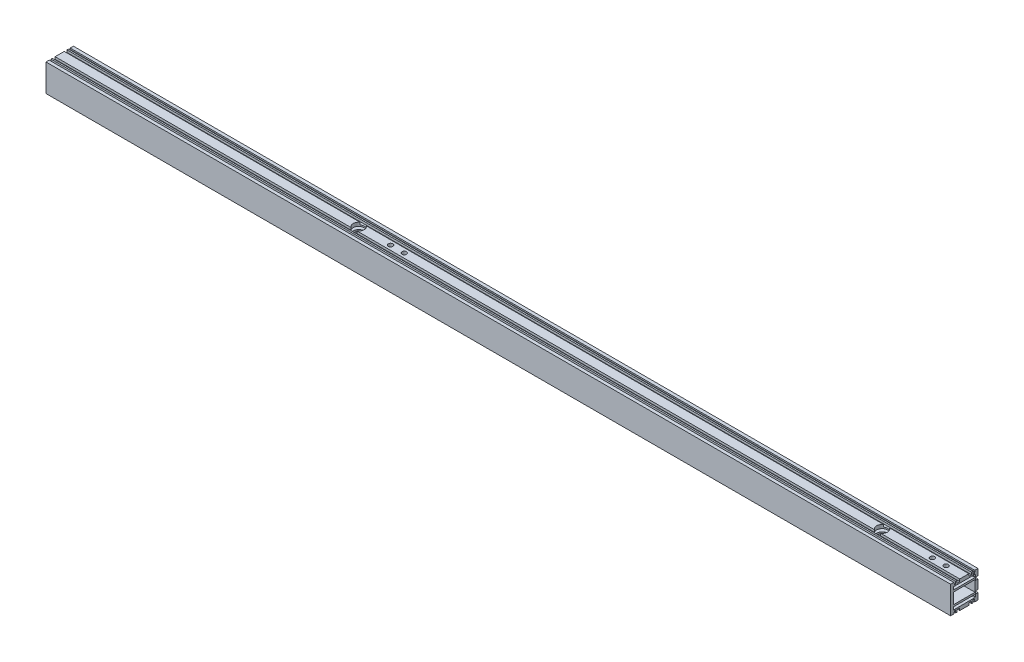
SolidWorks part; units mm, degrees
ref_plane "前视基准面" through (0, 0, 0) normal (0, 0, 1) x (1, 0, 0)
ref_plane "上视基准面" through (0, 0, 0) normal (0, 1, 0) x (1, 0, 0)
ref_plane "右视基准面" through (0, 0, 0) normal (1, 0, 0) x (0, 0, -1)
sketch "草图1" plane through (0, 0, 0) normal (1, 0, 0) x (0, 0, -1)
  line L0 (-15, 15) -> (15, -15) construction
  line L1 (-15, 15) -> (-11.5, 15)
  line L2 (-15, 15) -> (-15, -15)
  line L3 (-15, -15) -> (-11.5, -15)
  line L4 (15, 15) -> (15, 8)
  line L5 (15, 15) -> (-15, -15) construction
  line L6 (-11.5, 15) -> (-11.5, 13.5)
  line L7 (-11.5, 13.5) -> (-11, 13.5)
  line L8 (-11, 13.5) -> (-11, 12)
  line L9 (-11, 12) -> (-9.5, 12)
  line L10 (-9.5, 12) -> (-9.5, 15)
  line L11 (-9.5, 15) -> (-8, 15)
  line L12 (-8, 15) -> (-8, 12.5)
  line L13 (-8, 12.5) -> (-5, 12.5)
  line L14 (-5, 12.5) -> (-5, 15)
  line L15 (-5, 15) -> (5, 15)
  line L16 (0, 21.5201) -> (0, -18.309) construction
  line L17 (0, 55) -> (0, -55) construction
  line L18 (5, 12.5) -> (5, 15)
  line L19 (8, 12.5) -> (5, 12.5)
  line L20 (8, 15) -> (8, 12.5)
  line L21 (9.5, 15) -> (8, 15)
  line L22 (9.5, 12) -> (9.5, 15)
  line L23 (11, 12) -> (9.5, 12)
  line L24 (11, 13.5) -> (11, 12)
  line L25 (11.5, 13.5) -> (11, 13.5)
  line L26 (11.5, 15) -> (11.5, 13.5)
  line L27 (8, 15) -> (9.5, 15)
  line L28 (11.5, 15) -> (15, 15)
  line L29 (-19.8303, 0) -> (22.13, 0) construction
  line L30 (55, 0) -> (-55, 0) construction
  line L31 (8, -15) -> (9.5, -15)
  line L32 (11.5, -15) -> (11.5, -13.5)
  line L33 (11.5, -13.5) -> (11, -13.5)
  line L34 (11, -13.5) -> (11, -12)
  line L35 (11, -12) -> (9.5, -12)
  line L36 (9.5, -12) -> (9.5, -15)
  line L37 (9.5, -15) -> (8, -15)
  line L38 (8, -15) -> (8, -12.5)
  line L39 (8, -12.5) -> (5, -12.5)
  line L40 (5, -12.5) -> (5, -15)
  line L41 (-5, -15) -> (5, -15)
  line L42 (-5, -12.5) -> (-5, -15)
  line L43 (-8, -12.5) -> (-5, -12.5)
  line L44 (-8, -15) -> (-8, -12.5)
  line L45 (-9.5, -15) -> (-8, -15)
  line L46 (-9.5, -12) -> (-9.5, -15)
  line L47 (-11, -12) -> (-9.5, -12)
  line L48 (-11, -13.5) -> (-11, -12)
  line L49 (-11.5, -13.5) -> (-11, -13.5)
  line L50 (-11.5, -15) -> (-11.5, -13.5)
  line L51 (-9.5, -15) -> (-8, -15)
  line L52 (-5, -15) -> (5, -15)
  line L53 (8, -15) -> (9.5, -15)
  line L54 (11.5, -15) -> (15, -15)
  line L55 (15, 8) -> (12.5, 8)
  line L56 (12.5, 8) -> (12.5, 5)
  line L57 (12.5, 5) -> (15, 5)
  line L58 (12.5, -5) -> (15, -5)
  line L59 (12.5, -8) -> (12.5, -5)
  line L60 (15, -8) -> (12.5, -8)
  line L61 (15, 5) -> (15, -5)
  line L62 (15, -8) -> (15, -15)
  line L63 (12, -10.5) -> (12, -8.5)
  line L64 (-11.5, 11) -> (11.5, 11)
  line L65 (-12, 10.5) -> (-12, 8.5)
  line L66 (-11.5, 8) -> (11.5, 8)
  line L67 (12, 10.5) -> (12, 8.5)
  line L68 (-11.5, -8) -> (11.5, -8)
  line L69 (-12, -10.5) -> (-12, -8.5)
  line L70 (-11.5, -11) -> (11.5, -11)
  line L72 (-11.75, 6) -> (11.75, 6)
  line L73 (-11.75, 6) -> (-11.75, -6)
  line L74 (-11.75, -6) -> (11.75, -6)
  line L75 (11.75, 6) -> (11.75, -6)
  arc A0 (12, 8.5) -> (11.5, 8) centre (11.5, 8.5) cw
  arc A1 (11.5, 11) -> (12, 10.5) centre (11.5, 10.5) cw
  arc A2 (-11.5, 11) -> (-12, 10.5) centre (-11.5, 10.5) ccw
  arc A3 (-11.5, 8) -> (-12, 8.5) centre (-11.5, 8.5) cw
  arc A8 (-11.5, -8) -> (-12, -8.5) centre (-11.5, -8.5) ccw
  arc A9 (-11.5, -11) -> (-12, -10.5) centre (-11.5, -10.5) cw
  arc A10 (11.5, -11) -> (12, -10.5) centre (11.5, -10.5) ccw
  arc A11 (12, -8.5) -> (11.5, -8) centre (11.5, -8.5) ccw
  point P69 (12, 11)
  point P72 (-12, 11)
  point P77 (-11, -13.5)
  point P80 (11, -13.5)
  point P83 (11, 13.5)
  point P86 (-11, 13.5)
  point P99 (-12, -11)
  point P100 (12, -11)
  dimension "D17" = 0.5
  dimension "D1" = 3.5
  dimension "D2" = 1.5
  dimension "D3" = 0.5
  dimension "D4" = 1.5
  dimension "D5" = 3
  dimension "D6" = 30
  dimension "D7" = 30
  dimension "D8" = 1.5
  dimension "D9" = 2.5
  dimension "D10" = 3
  dimension "D11" = 2.5
  dimension "D12" = 7
  dimension "D13" = 3
  dimension "D14" = 4
  dimension "D15" = 3
  dimension "D16" = 24
  dimension "D19" = 23.5
  dimension "D20" = 12
extrude "凸台-拉伸1" add sketch "草图1" along normal mid plane 991 contours L2 L3 L50 L49 L48 L47 L46 L45 L44 L43 L42 L41 L40 L39 L38 L31 L36 L35 L34 L33 L32 L54 L62 L60 L59 L58 L61 L57 L56 L55 L4 L28 L26 L25 L24 L23 L22 L21 L20 L19 L18 L15 L14 L13 region at (0, 14.5757, 13.25)
hole_wizard "M6 螺纹孔1" positions "草图3" profile "草图2" tap size "M6" standard "GB"
sketch "草图3" plane through (0, 0, -15) normal (0, 0, -1) x (-1, 0, 0)
  line L0 (-495.5, -15) -> (495.5, -15) construction
  line L1 (495.5, 5) -> (495.5, -5) construction
  point P2 (445.5, 0)
  point P5 (430.5, 0)
  point P8 (370.5, 0)
  point P10 (266.5, 0)
  point P17 (394.5, 0)
  dimension "D1" = 15
  dimension "D2" = 15
  dimension "D3" = 104
  dimension "D4" = 125
  dimension "D5" = 15
  dimension "D6" = 101
sketch "草图2" plane through (-445.5, 0, -15) normal (1, 0, 0) x (0, 1, 0)
  line L0 (0, 0) -> (0, 20.5022)
  line L1 (0, 20.5022) -> (2.5, 19)
  line L2 (2.5, 19) -> (2.5, 0)
  line L5 (2.5, 0) -> (0, 0)
  line L10 (0, 20.5022) -> (-2.5, 19) construction
  line L11 (0, -6.35) -> (0, 107.95) construction
  dimension "螺纹孔钻头直径" = 5
  dimension "螺纹孔钻头深度" = 19
  dimension "导头角度" = 118
cosmetic thread "孔螺蚊线1" parameters "D1"=3.25, "D2"=6
cosmetic thread "孔螺蚊线2" parameters "D1"=3.25, "D2"=6
cosmetic thread "孔螺蚊线13" parameters "D1"=3.25, "D2"=6
cosmetic thread "孔螺蚊线14" parameters "D1"=3.25, "D2"=6
cosmetic thread "孔螺蚊线22" parameters "D1"=3.25, "D2"=6
hole_wizard "M6 螺纹孔2" positions "草图5" profile "草图4" tap size "M6" standard "GB"
sketch "草图5" plane through (0, 15, 0) normal (0, 1, 0) x (1, 0, 0)
  point P0 (-133, 0)
  point P3 (-118, 0)
  point P6 (460.5, 0)
  point P9 (475.5, 0)
sketch "草图4" plane through (-133, 15, 0) normal (1, 0, 0) x (0, 0, 1)
  line L0 (0, 0) -> (0, 20.5022)
  line L1 (0, 20.5022) -> (2.5, 19)
  line L2 (2.5, 19) -> (2.5, 0)
  line L5 (2.5, 0) -> (0, 0)
  line L10 (0, 20.5022) -> (-2.5, 19) construction
  line L11 (0, -6.35) -> (0, 107.95) construction
  dimension "螺纹孔钻头直径" = 5
  dimension "螺纹孔钻头深度" = 19
  dimension "导头角度" = 118
cosmetic thread "孔螺蚊线3" parameters "D1"=9, "D2"=6
cosmetic thread "孔螺蚊线4" parameters "D1"=9, "D2"=6
cosmetic thread "孔螺蚊线5" parameters "D1"=9, "D2"=6
cosmetic thread "孔螺蚊线6" parameters "D1"=9, "D2"=6
hole_wizard "M6 螺纹孔3" positions "草图7" profile "草图6" tap size "M6" standard "GB"
sketch "草图7" plane through (0, -15, 0) normal (0, -1, 0) x (-1, 0, 0)
  point P0 (445.5, 0)
  point P3 (430.5, 0)
  point P6 (-230.5, 0)
  point P9 (-245.5, 0)
  point P12 (-460.5, 0)
  point P15 (-475.5, 0)
sketch "草图6" plane through (-445.5, -15, 0) normal (1, 0, 0) x (0, 0, -1)
  line L0 (0, 0) -> (0, 20.5022)
  line L1 (0, 20.5022) -> (2.5, 19)
  line L2 (2.5, 19) -> (2.5, 0)
  line L5 (2.5, 0) -> (0, 0)
  line L10 (0, 20.5022) -> (-2.5, 19) construction
  line L11 (0, -6.35) -> (0, 107.95) construction
  dimension "螺纹孔钻头直径" = 5
  dimension "螺纹孔钻头深度" = 19
  dimension "导头角度" = 118
cosmetic thread "孔螺蚊线7" parameters "D1"=9, "D2"=6
cosmetic thread "孔螺蚊线8" parameters "D1"=9, "D2"=6
cosmetic thread "孔螺蚊线9" parameters "D1"=9, "D2"=6
cosmetic thread "孔螺蚊线10" parameters "D1"=9, "D2"=6
cosmetic thread "孔螺蚊线11" parameters "D1"=9, "D2"=6
cosmetic thread "孔螺蚊线12" parameters "D1"=9, "D2"=6
hole_wizard "M4 螺纹孔1" positions "草图11" profile "草图10" tap size "M4" standard "GB"
sketch "草图11" plane through (0, 0, -15) normal (0, 0, -1) x (-1, 0, 0)
  line L0 (495.5, 5) -> (495.5, -5) construction
  line L1 (-495.5, -15) -> (495.5, -15) construction
  point P0 (191, 0)
  point P2 (236, 0)
  point P20 (341, 0)
  point P22 (296, 0)
  dimension "D1" = 259.5
  dimension "D2" = 15
  dimension "D3" = 15
  dimension "D4" = 45
  dimension "D5" = 45
  dimension "D6" = 15
  dimension "D7" = 15
  dimension "D8" = 154.5
sketch "草图10" plane through (-191, 0, -15) normal (1, 0, 0) x (0, 1, 0)
  line L0 (0, 0) -> (0, 15.9914)
  line L1 (0, 15.9914) -> (1.65, 15)
  line L2 (1.65, 15) -> (1.65, 0)
  line L5 (1.65, 0) -> (0, 0)
  line L10 (0, 15.9914) -> (-1.65, 15) construction
  line L11 (0, -6.35) -> (0, 107.95) construction
  dimension "螺纹孔钻头直径" = 3.3
  dimension "螺纹孔钻头深度" = 15
  dimension "导头角度" = 118
cosmetic thread "孔螺蚊线19" parameters "D1"=3.25, "D2"=4
cosmetic thread "孔螺蚊线20" parameters "D1"=3.25, "D2"=4
cosmetic thread "孔螺蚊线23" parameters "D1"=3.25, "D2"=4
cosmetic thread "孔螺蚊线24" parameters "D1"=3.25, "D2"=4
hole_wizard "Ø12.0 (12) 直径孔1" positions "草图13" profile "草图12" hole size "Ø12.0" standard "GB" end condition through all
sketch "草图13" plane through (0, -15, 0) normal (0, -1, 0) x (-1, 0, 0)
  line L0 (-495.5, 15) -> (495.5, 15) construction
  line L1 (-495.5, 11.5) -> (-495.5, 15) construction
  line L2 (495.5, -5) -> (495.5, 5) construction
  point P0 (168, 0)
  point P9 (-405.5, 0)
  dimension "D1" = 15
  dimension "D2" = 90
  dimension "D3" = 15
  dimension "D4" = 327.5
sketch "草图12" plane through (-168, -15, 0) normal (1, 0, 0) x (0, 0, -1)
  line L0 (0, 0) -> (0, 30)
  line L1 (0, 30) -> (6, 30)
  line L2 (6, 30) -> (6, 0)
  line L5 (6, 0) -> (0, 0)
  line L11 (0, -6.35) -> (0, 107.95) construction
  dimension "通孔孔直径" = 12
  dimension "通孔孔深度" = 30
